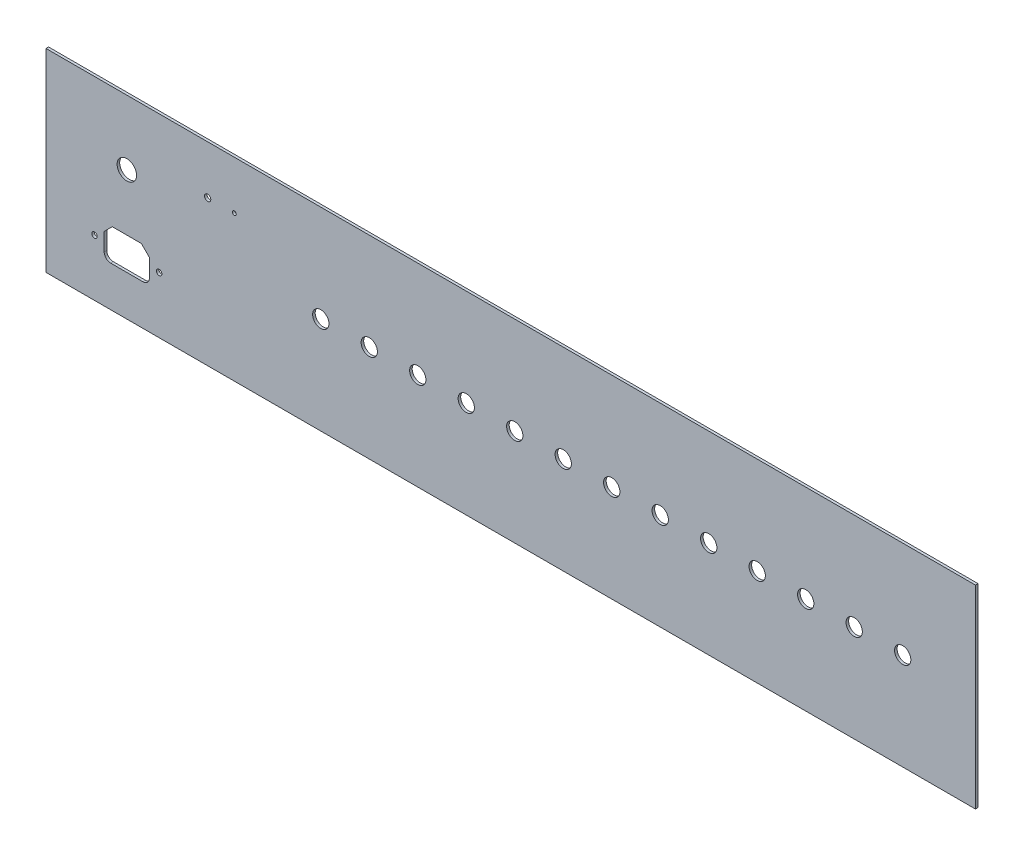
SolidWorks part; units mm, degrees
ref_plane "Front Plane" through (0, 0, 0) normal (0, 0, 1) x (1, 0, 0)
ref_plane "Top Plane" through (0, 0, 0) normal (0, 1, 0) x (1, 0, 0)
ref_plane "Right Plane" through (0, 0, 0) normal (1, 0, 0) x (0, 0, -1)
sketch "Sketch1" plane through (0, 0, 0) normal (0, 0, 1) x (1, 0, 0)
  line L1 (287.5, -60) -> (-287.5, -60)
  line L2 (287.5, -60) -> (287.5, 60)
  line L3 (287.5, 60) -> (-287.5, 60)
  line L4 (-287.5, -60) -> (-287.5, 60)
  line L5 (287.5, -60) -> (-287.5, 60) construction
  line L6 (287.5, 60) -> (-287.5, -60) construction
  point P0 (0, 0)
  dimension "D1" = 120
  dimension "D2" = 575
extrude "Boss-Extrude1" add sketch "Sketch1" along normal blind 1.5875
hole_wizard "M3 Clearance Hole1" positions "Sketch2" profile "Sketch3" hole size "M3" standard "ANSI Metric" end condition through all
sketch "Sketch2" plane through (0, 0, 1.5875) normal (0, 0, 1) x (1, 0, 0)
  line L0 (-287.5, 60) -> (-287.5, -60) construction
  line L1 (287.5, 60) -> (-287.5, 60) construction
  point P0 (-257.5, -25)
  point P2 (-217.5, -25)
  dimension "D1" = 40
  dimension "D2" = 30
  dimension "D3" = 85
sketch "Sketch3" plane through (-257.5, -25, 1.5875) normal (1, 0, 0) x (0, -1, 0)
  line L0 (0, 0) -> (0, 1.5875)
  line L1 (0, 1.5875) -> (1.7, 1.5875)
  line L2 (1.7, 1.5875) -> (1.7, 0)
  line L5 (1.7, 0) -> (0, 0)
  line L11 (0, -6.35) -> (0, 107.95) construction
  dimension "Thru Hole Dia." = 3.4
  dimension "Thru Hole Depth" = 1.5875
hole_wizard "3/8 Clearance Hole1" positions "Sketch4" profile "Sketch5" hole size "3/8" standard "ANSI Inch" end condition through all
sketch "Sketch4" plane through (0, 0, 1.5875) normal (0, 0, 1) x (1, 0, 0)
  line L0 (-287.5, 60) -> (-287.5, -60) construction
  point P0 (-117.5, 0)
  dimension "D1" = 170
sketch "Sketch5" plane through (-117.5, 0, 1.5875) normal (1, 0, 0) x (0, -1, 0)
  line L0 (0, 0) -> (0, 1.5875)
  line L1 (0, 1.5875) -> (5.0419, 1.5875)
  line L2 (5.0419, 1.5875) -> (5.0419, 0)
  line L5 (5.0419, 0) -> (0, 0)
  line L11 (0, -6.35) -> (0, 107.95) construction
  dimension "Thru Hole Dia." = 10.0838
  dimension "Thru Hole Depth" = 1.5875
pattern_linear "LPattern1" count 13 spacing 30 along (1, 0, 0) of "3/8 Clearance Hole1"
sketch "Sketch8" plane through (0, 0, 1.5875) normal (0, 0, 1) x (1, 0, 0)
  line L0 (287.5, 60) -> (-287.5, 60) construction
  line L1 (-287.5, 60) -> (-287.5, -60) construction
  circle A0 centre (-187.5, 30) radius 1.95
  circle A1 centre (-170.99, 30) radius 1.2
  dimension "D1" = 16.51
  dimension "D2" = 30
  dimension "D3" = 100
extrude "Cut-Extrude1" cut sketch "Sketch8" against normal up to next
sketch "Sketch9" plane through (0, 0, 1.5875) normal (0, 0, 1) x (1, 0, 0)
  line L1 (-223.5, -35) -> (-251.5, -35)
  line L2 (-223.5, -35) -> (-223.5, -15)
  line L3 (-223.5, -15) -> (-251.5, -15)
  line L4 (-251.5, -35) -> (-251.5, -15)
  line L5 (-223.5, -35) -> (-251.5, -15) construction
  line L6 (-223.5, -15) -> (-251.5, -35) construction
  circle A0 centre (-217.5, -25) radius 1.7 construction
  circle A1 centre (-257.5, -25) radius 1.7 construction
  point P0 (-237.5, -25)
  dimension "D1" = 20
  dimension "D2" = 28
  dimension "D3" = 20
  dimension "D4" = 0
extrude "Cut-Extrude2" cut sketch "Sketch9" against normal up to next
fillet "Fillet1" radius 4 2 edges at (-223.5, -35, 0.7937) (-251.5, -35, 0.7937)
chamfer "Chamfer1" distance 5 angle 45 2 edges at (-223.5, -15, 0.7937) (-251.5, -15, 0.7937)
sketch "Sketch10" plane through (0, 0, 1.5875) normal (0, 0, 1) x (1, 0, 0)
  line L0 (-287.5, 60) -> (-287.5, -60) construction
  line L1 (287.5, 60) -> (-287.5, 60) construction
  circle A0 centre (-237.5, 20) radius 6
  dimension "D1" = 50
  dimension "D2" = 40
extrude "Cut-Extrude3" cut sketch "Sketch10" against normal up to next
